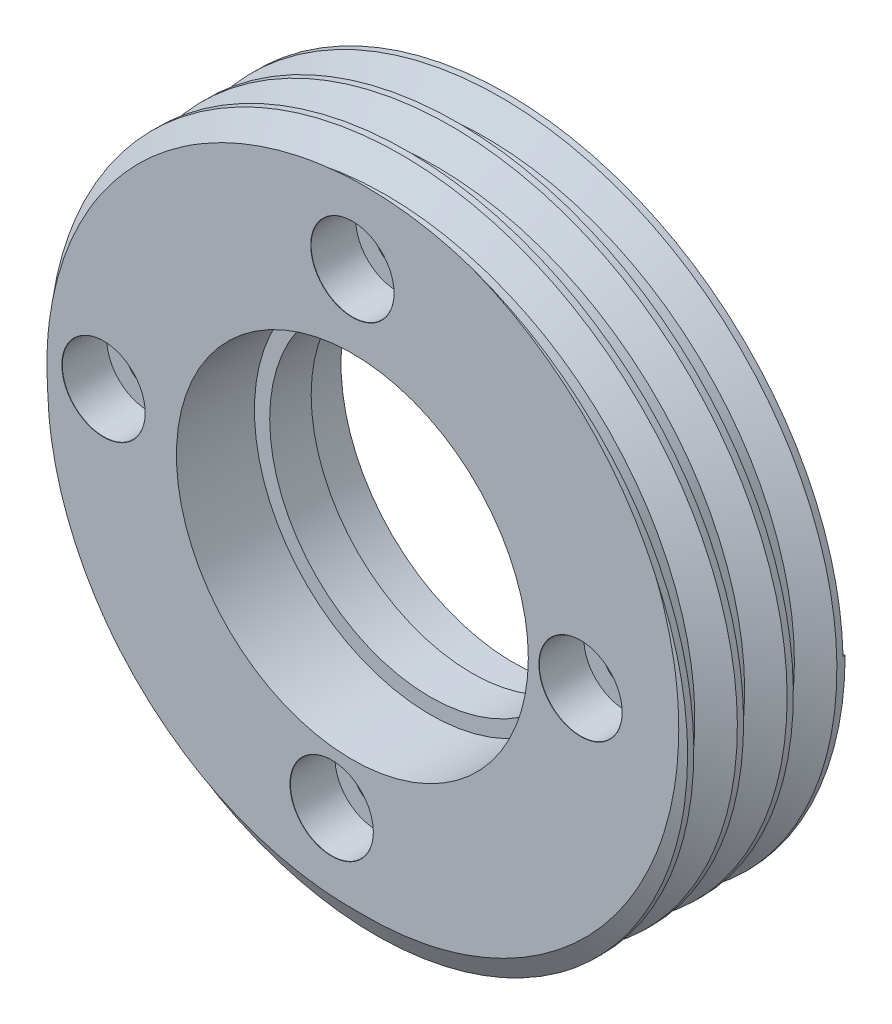
SolidWorks part; units mm, degrees
ref_plane "Front Plane" through (0, 0, 0) normal (0, 0, 1) x (1, 0, 0)
ref_plane "Top Plane" through (0, 0, 0) normal (0, 1, 0) x (1, 0, 0)
ref_plane "Right Plane" through (0, 0, 0) normal (1, 0, 0) x (0, 0, -1)
sketch "Sketch1" plane through (0, 0, 0) normal (0, 0, 1) x (1, 0, 0)
  circle A0 centre (0, 0) radius 40
  circle A1 centre (0, 0) radius 20.7645
  circle A2 centre (0, 0) radius 20.7645 construction
  dimension "D2" = 80
extrude "Boss-Extrude1" add sketch "Sketch1" along normal blind 5
sketch "Sketch2" plane through (0, 0, 5) normal (0, 0, 1) x (1, 0, 0)
  circle A0 centre (0, 0) radius 19.3675
  circle A1 centre (0, 0) radius 40
  circle A2 centre (0, 0) radius 40
  dimension "D2" = 38.735
  dimension "D1" = 0
extrude "Boss-Extrude2" add sketch "Sketch2" along normal blind 5
sketch "Sketch3" plane through (0, 0, 10) normal (0, 0, 1) x (1, 0, 0)
  circle A0 centre (0, 0) radius 40 construction
  circle A1 centre (0, 0) radius 40
  circle A2 centre (0, 0) radius 21.209
  dimension "D1" = 42.418
extrude "Boss-Extrude3" add sketch "Sketch3" along normal blind 9.398
sketch "Sketch4" plane through (0, 0, 19.398) normal (0, 0, 1) x (1, 0, 0)
  circle A0 centre (0, 30) radius 2.5
  circle A1 centre (27.5, 0) radius 2.5
  circle A2 centre (-2.5, -27.5) radius 2.5
  circle A3 centre (-30, 2.5) radius 2.5
  point P0 (0, 30)
  point P7 (27.5, 0)
  point P9 (-2.5, -27.5)
  point P11 (-30, 2.5)
  point P13 (-1.25, 1.25)
  dimension "D2" = 5
  dimension "D1" = 30
  dimension "D3" = 4
hole_wizard "CBORE for M5 Hex Socket Head Cap Screw1" positions "Sketch4" profile "Sketch6" counterbore size "M5" standard "DIN" end condition through all
sketch "Sketch6" plane through (0, 30, 19.398) normal (1, 0, 0) x (0, -1, 0)
  line L0 (0, 0) -> (0, 19.398)
  line L1 (0, 19.398) -> (2.75, 19.398)
  line L3 (2.75, 19.398) -> (2.75, 5.4)
  line L4 (5, 5.4) -> (2.75, 5.4)
  line L5 (5, 5.4) -> (5, 0.025)
  line L6 (5, 0.025) -> (5.025, 0)
  line L7 (5.025, 0) -> (0, 0)
  line L8 (-5, 0.025) -> (-5.025, 0) construction
  line L11 (0, -6.35) -> (0, 107.95) construction
  dimension "Thru Hole Dia." = 5.5
  dimension "Thru Hole Depth" = 19.398
  dimension "C'Bore Dia." = 10
  dimension "C'Bore Depth" = 5.4
  dimension "Near C'Sink Dia." = 10.05
  dimension "Near C'Sink Angle" = 90
thread "Thread1" pitch 6 method cut profile "Thread Profile1" start angle 0, offset 5, length 30, pitch 6, diameter 80
ref_plane "Plane1" through (40, 0, -5) normal (0, -1, 0) x (1, 0, 0)
sketch "Thread Profile1" plane through (40, 0, -5) normal (0, -1, 0) x (1, 0, 0)
  line L0 (0, 0) -> (0, 6) construction
  line L11 (0, 0) -> (0, 5.25)
  line L12 (0, 5.25) -> (-3.2476, 3.375)
  line L13 (-3.2476, 3.375) -> (-3.2476, 1.875)
  line L15 (-3.2476, 1.875) -> (0, 0)
  line L17 (-3.2476, 2.625) -> (0, 2.625) construction
  point P2 (0, 0)
  dimension "Pitch" = 6
  dimension "Profile_Angle" = 60
  dimension "Profile_Land" = 1.5
  dimension "Profile_Height" = 3.2476
